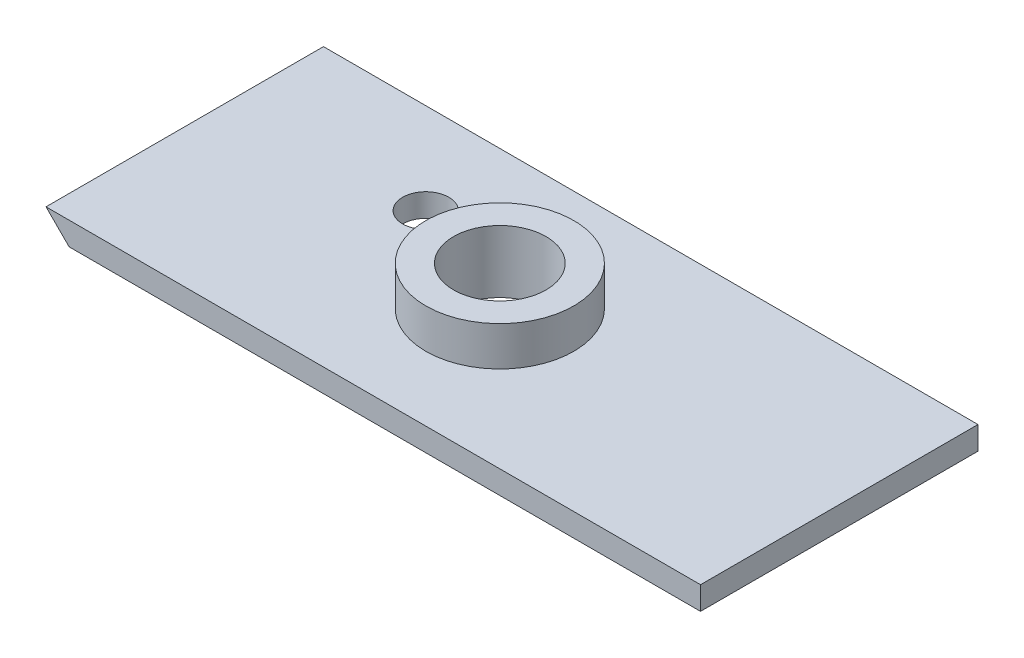
SolidWorks part; units mm, degrees
ref_plane "前视基准面" through (0, 0, 0) normal (0, 0, 1) x (1, 0, 0)
ref_plane "上视基准面" through (0, 0, 0) normal (0, 1, 0) x (1, 0, 0)
ref_plane "右视基准面" through (0, 0, 0) normal (1, 0, 0) x (0, 0, -1)
sketch "草图2" plane through (0, 0, 0) normal (0, 1, 0) x (1, 0, 0)
  line L0 (-21.1496, -1.9474) -> (21.7063, -1.9474) construction
  line L1 (-18.5276, 4.0526) -> (11.4724, 4.0526)
  line L2 (-18.5276, 4.0526) -> (-18.5276, -7.9474)
  line L3 (-18.5276, -7.9474) -> (11.4724, -7.9474)
  line L4 (11.4724, 4.0526) -> (11.4724, -7.9474)
  circle A1 centre (-5.2076, -1.9474) radius 2
  circle A2 centre (-5.2076, -1.9474) radius 3.2 construction
  dimension "D3" = 13.32
  dimension "D4" = 4
  dimension "D5" = 6.4
  dimension "D1" = 30
  dimension "D2" = 12
extrude "凸台-拉伸1" add sketch "草图2" along normal blind 1
sketch "草图3" plane through (0, 1, 0) normal (0, 1, 0) x (1, 0, 0)
  circle A0 centre (-5.2076, -1.9474) radius 2
  circle A1 centre (-5.2076, -1.9474) radius 3.2
extrude "凸台-拉伸2" add sketch "草图3" along normal blind 1.7
sketch "草图4" plane through (0, 0, 0) normal (0, -1, 0) x (1, 0, 0)
  line L0 (-18.5276, -4.0526) -> (-18.5276, 7.9474) construction
  line L6 (11.4724, -4.0526) -> (-18.5276, -4.0526) construction
  circle A0 centre (-10.4812, -0.1227) radius 1
  dimension "D1" = 8.0464
  dimension "D2" = 3.9299
extrude "切除-拉伸1" cut sketch "草图4" against normal blind 5
sketch "草图5" plane through (0, 0, -4.0526) normal (0, 0, -1) x (-1, 0, 0)
  line L0 (18.5276, 1) -> (18.5276, 0)
  line L1 (18.5276, 0) -> (19.5276, 1)
  line L2 (19.5276, 1) -> (18.5276, 1)
  dimension "D1" = 1
extrude "凸台-拉伸3" add sketch "草图5" against normal blind 12
sketch "草图6" plane through (0, 0, 0) normal (0, -1, 0) x (1, 0, 0)
  line L0 (11.4724, -4.0526) -> (-18.5276, -4.0526) construction
  line L1 (11.4724, 7.9474) -> (9.4724, 7.9474)
  line L2 (11.4724, 7.9474) -> (11.4724, -4.0526)
  line L3 (11.4724, -4.0526) -> (9.4724, -4.0526)
  line L4 (9.4724, 7.9474) -> (9.4724, -4.0526)
  dimension "D1" = 2
extrude "切除-拉伸2" cut sketch "草图6" against normal blind 1
sketch "草图7" plane through (0, 0, -4.0526) normal (0, 0, -1) x (-1, 0, 0)
  line L0 (19.5276, 1) -> (18.5276, 0)
  line L1 (18.5276, 0) -> (17.8346, 0)
  line L2 (-9.4724, 0) -> (18.5276, 0) construction
  line L3 (17.8346, 0) -> (18.8346, 1)
  line L4 (-9.4724, 1) -> (19.5276, 1) construction
  line L5 (18.8346, 1) -> (19.5276, 1)
  dimension "D1" = 0.49
extrude "切除-拉伸3" cut sketch "草图7" against normal blind 12
